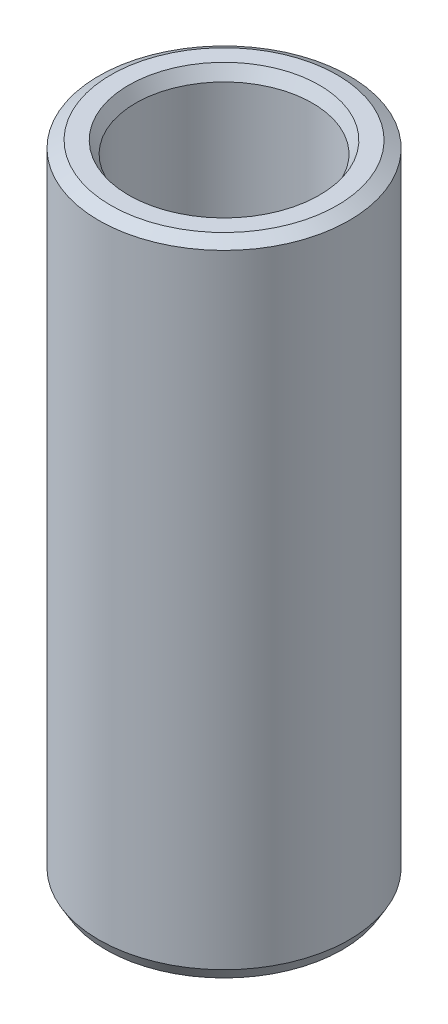
SolidWorks part; units mm, degrees
ref_plane "Front Plane" through (0, 0, 0) normal (0, 0, 1) x (1, 0, 0)
ref_plane "Top Plane" through (0, 0, 0) normal (0, 1, 0) x (1, 0, 0)
ref_plane "Right Plane" through (0, 0, 0) normal (1, 0, 0) x (0, 0, -1)
sketch "Sketch1" plane through (0, 0, 0) normal (0, 1, 0) x (1, 0, 0)
  circle A0 centre (0, 0) radius 45
  dimension "SLEEVE_OD" = 90
extrude "Boss-Extrude1" add sketch "Sketch1" along normal blind 230.6872
sketch "Sketch2" plane through (0, 0, 0) normal (0, 1, 0) x (1, 0, 0)
  circle A0 centre (0, 0) radius 31.7598
  dimension "BORE_D" = 63.5197
extrude "Cut-Extrude1" cut sketch "Sketch2" along normal through all
chamfer "Chamfer1" distance 2.5049 angle 60 4 edges at (0, 230.6872, 31.7598) (0, 0, 31.7598) (0, 0, 45) (0, 230.6872, 45) first distance on face at (0, 230.6872, 31.7598) first distance on face at (0, 0, 31.7598) first distance on face at (0, 230.6872, 45)
